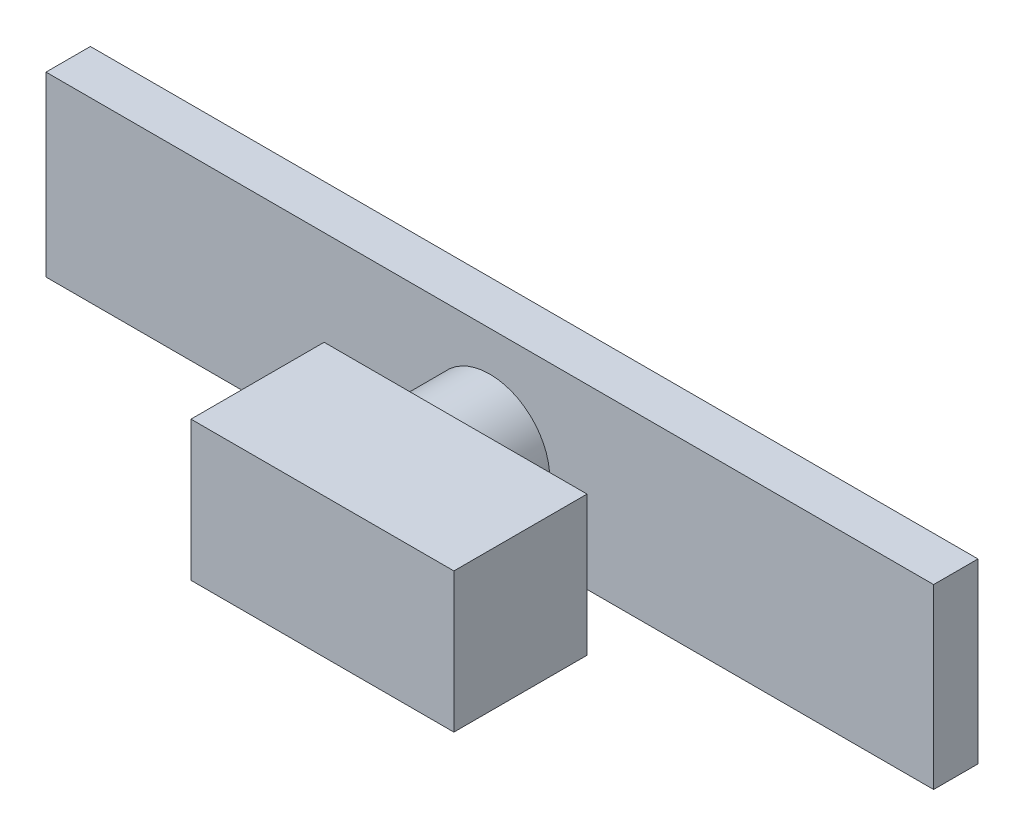
SolidWorks part; units mm, degrees
ref_plane "Front Plane" through (0, 0, 0) normal (0, 0, 1) x (1, 0, 0)
ref_plane "Top Plane" through (0, 0, 0) normal (0, 1, 0) x (1, 0, 0)
ref_plane "Right Plane" through (0, 0, 0) normal (1, 0, 0) x (0, 0, -1)
sketch "Sketch2" plane through (0, 0, 0) normal (0, 0, 1) x (1, 0, 0)
  line L1 (-47.8692, 21.2481) -> (206.1308, 21.2481)
  line L2 (-47.8692, 21.2481) -> (-47.8692, 8.5481)
  line L3 (-47.8692, 8.5481) -> (206.1308, 8.5481)
  line L4 (206.1308, 21.2481) -> (206.1308, 8.5481)
  dimension "D1" = 12.7
  dimension "D2" = 254
extrude "Boss-Extrude1" add sketch "Sketch2" along normal blind 50.8
sketch "Sketch3" plane through (0, 21.2481, 0) normal (0, 1, 0) x (1, 0, 0)
  circle A0 centre (79.1308, -28.4831) radius 17.1408
extrude "Boss-Extrude2" add sketch "Sketch3" along normal blind 19.05
sketch "Sketch4" plane through (0, 40.2981, 0) normal (0, 1, 0) x (1, 0, 0)
  line L1 (50.7675, -8.111) -> (126.0034, -8.111)
  line L2 (50.7675, -8.111) -> (50.7675, -48.0661)
  line L3 (50.7675, -48.0661) -> (126.0034, -48.0661)
  line L4 (126.0034, -8.111) -> (126.0034, -48.0661)
extrude "Boss-Extrude3" add sketch "Sketch4" along normal blind 38.1
scale "Scale2" scale about centroid uniform scaling yes scale factor 0.06
move or copy body "Body-Move/Copy1" bodies to move or copy 105 copy no rotation origin (0, 33.6669, 26.5501) rotation axis (1, 0, 0) rotation angle 90
move or copy body "Body-Move/Copy3" bodies to move or copy 106 copy no translate (-50.8, 0, -50.8)
scale "Scale5" scale about centroid uniform scaling yes scale factor 0.25
move or copy body "Body-Move/Copy9" bodies to move or copy 111 copy no translate (-50.8, 0, 0)
move or copy body "Body-Move/Copy13" bodies to move or copy 117 copy no translate (0, -50.8, 0)
scale "Scale6" bodies to scale 121 scale about centroid uniform scaling yes scale factor 0.25
move or copy body "Body-Move/Copy16" bodies to move or copy 122 copy no translate (0, 0, -12.7)
